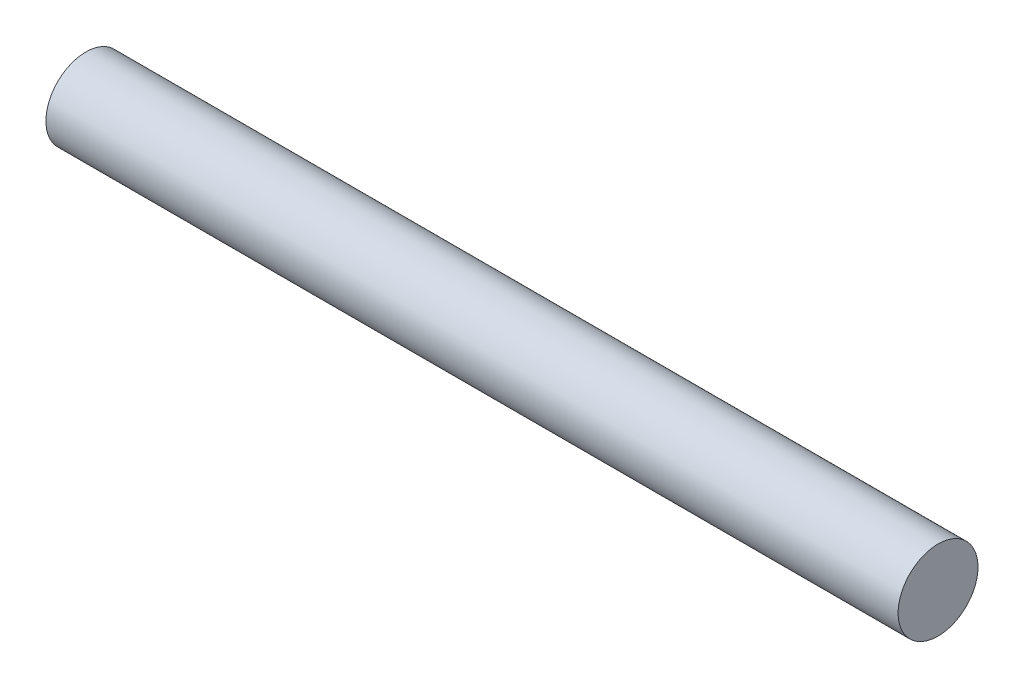
SolidWorks part; units mm, degrees
material "Brass"
ref_plane "Front" through (0, 0, 0) normal (0, 0, 1) x (1, 0, 0)
ref_plane "Top" through (0, 0, 0) normal (0, 1, 0) x (1, 0, 0)
ref_plane "Right" through (0, 0, 0) normal (1, 0, 0) x (0, 0, -1)
sketch "Sketch1" plane through (0, 0, 0) normal (1, 0, 0) x (0, 0, -1)
  circle A0 centre (0, 0) radius 1.5
  dimension "D1" = 3
extrude "Boss-Extrude1" add sketch "Sketch1" along normal mid plane 32
